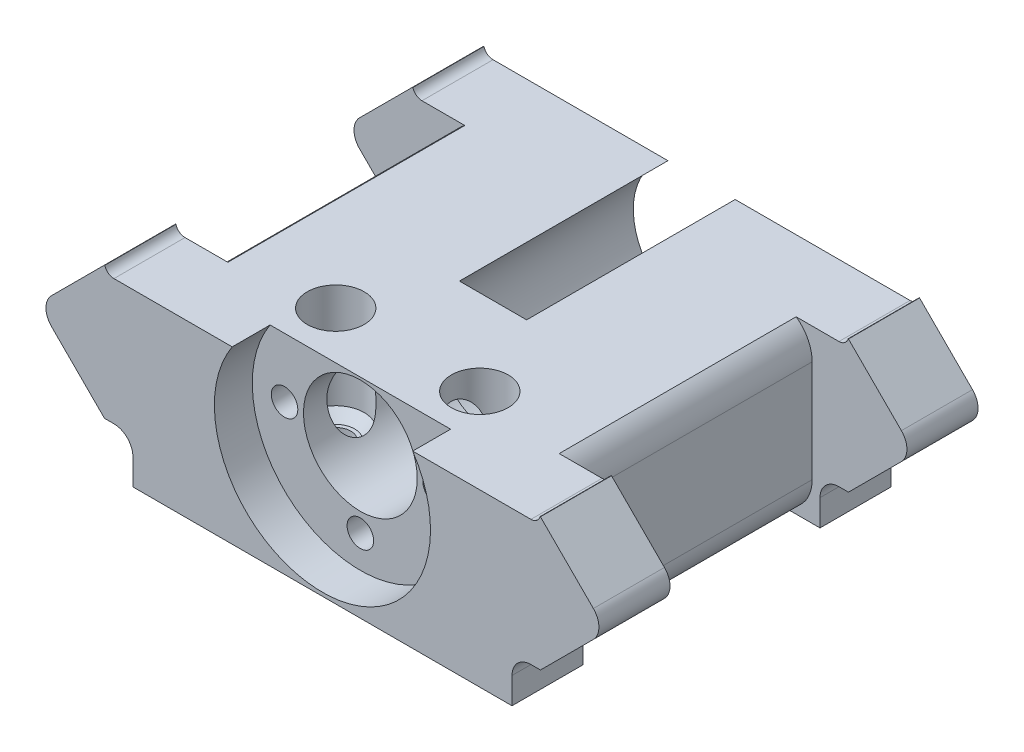
SolidWorks part; units mm, degrees
ref_plane "Front Plane" through (0, 0, 0) normal (0, 0, 1) x (1, 0, 0)
ref_plane "Top Plane" through (0, 0, 0) normal (0, 1, 0) x (1, 0, 0)
ref_plane "Right Plane" through (0, 0, 0) normal (1, 0, 0) x (0, 0, -1)
sketch "Sketch3" plane through (0, 0, 0) normal (0, 0, 1) x (1, 0, 0)
  line L0 (0, 10) -> (0, -10) construction
  line L3 (30, 0) -> (0, 0) construction
  line L5 (-30, 0) -> (30, 0) construction
  line L6 (-28.5858, 1.4142) -> (-23, 7)
  line L7 (-23, 7) -> (23, 7)
  line L8 (0, 10) -> (0, -10) construction
  line L9 (28.5858, 1.4142) -> (23, 7)
  line L10 (28.5858, -1.4142) -> (23, -7)
  line L11 (-28.5858, -1.4142) -> (-23, -7)
  line L12 (-23, -7) -> (-22, -7)
  line L13 (22, -7) -> (23, -7)
  line L14 (-20, -11.77) -> (20, -11.77)
  line L15 (-20, -10) -> (-20, -9)
  line L16 (20, -10) -> (20, -9)
  line L17 (20, -11.77) -> (20, -10)
  line L18 (-20, -11.77) -> (-20, -10)
  arc A0 (-20, -9) -> (-22, -7) centre (-22, -9) ccw
  arc A1 (20, -9) -> (22, -7) centre (22, -9) cw
  arc A2 (28.5858, -1.4142) -> (28.5858, 1.4142) centre (27.1716, 0) ccw
  arc A3 (-28.5858, -1.4142) -> (-28.5858, 1.4142) centre (-27.1716, 0) cw
  circle A4 centre (0, 0) radius 6
  point P17 (0, 7)
  dimension "D3" = 2
  dimension "D4" = 1.77
  dimension "D1" = 45
  dimension "D2" = 46
extrude "Boss-Extrude1" add sketch "Sketch3" along normal blind 40
sketch "Sketch4" plane through (0, -11.77, 0) normal (0, -1, 0) x (1, 0, 0)
  line L0 (-29.1716, 40) -> (-29.1716, 0) construction
  line L1 (-39.1716, 32.5) -> (-19.1716, 32.5)
  line L2 (-39.1716, 32.5) -> (-39.1716, 7.5)
  line L3 (-39.1716, 7.5) -> (-19.1716, 7.5)
  line L4 (-19.1716, 32.5) -> (-19.1716, 7.5)
  line L5 (-39.1716, 32.5) -> (-19.1716, 7.5) construction
  line L6 (-39.1716, 7.5) -> (-19.1716, 32.5) construction
  line L7 (0, 40) -> (0, 0) construction
  line L8 (-20, 40) -> (20, 40) construction
  line L9 (39.1716, 32.5) -> (39.1716, 7.5)
  line L10 (39.1716, 7.5) -> (19.1716, 7.5)
  line L11 (19.1716, 32.5) -> (19.1716, 7.5)
  line L12 (39.1716, 32.5) -> (19.1716, 32.5)
  point P0 (-29.1716, 20)
  dimension "D1" = 20
  dimension "D2" = 25
extrude "Cut-Extrude1" cut sketch "Sketch4" against normal up to next
fillet "Fillet1" radius 4 4 edges at (19.1716, 7, 20) (19.1716, -11.77, 20) (-19.1716, -11.77, 20) (-19.1716, 7, 20)
sketch "Sketch5" plane through (0, 0, 40) normal (0, 0, 1) x (1, 0, 0)
  circle A0 centre (0, 0) radius 11.4
extrude "Cut-Extrude2" cut sketch "Sketch5" against normal blind 4
sketch "Sketch6" plane through (0, 0, 36) normal (0, 0, 1) x (1, 0, 0)
  circle A0 centre (0, 0) radius 8 construction
  circle A1 centre (0, -8) radius 1.4
  circle A2 centre (-8, 0) radius 1.4
  circle A3 centre (8, 0) radius 1.4
extrude "Cut-Extrude3" cut sketch "Sketch6" against normal blind 14
sketch "Sketch7" plane through (0, 0, 0) normal (0, 0, -1) x (-1, 0, 0)
  line L0 (-23, 7) -> (23, 7) construction
  line L1 (-22.9991, 7.7333) -> (22.9991, 7.7333)
  line L2 (-22.9991, 7.7333) -> (-22.9991, 7.2667)
  line L3 (-21.9991, 6.2667) -> (21.9991, 6.2667)
  line L4 (22.9991, 7.7333) -> (22.9991, 7.2667)
  line L5 (-22.9991, 7.7333) -> (22.9991, 6.2667) construction
  line L6 (-22.9991, 6.2667) -> (22.9991, 7.7333) construction
  arc A0 (22.9991, 7.2667) -> (21.9991, 6.2667) centre (21.9991, 7.2667) cw
  arc A1 (-22.9991, 7.2667) -> (-21.9991, 6.2667) centre (-21.9991, 7.2667) ccw
  point P0 (0, 7)
  dimension "D1" = 1
extrude "Cut-Extrude4" cut sketch "Sketch7" against normal up to next
sketch "Sketch8" plane through (0, 0, 0) normal (0, 0, -1) x (-1, 0, 0)
  circle A0 centre (0, 0) radius 7.2
extrude "Cut-Extrude5" cut sketch "Sketch8" against normal blind 22
sketch "Эскиз1" plane through (0, -11.77, 0) normal (0, -1, 0) x (1, 0, 0)
  line L0 (0, 40) -> (0, 0) construction
  line L1 (-20, 40) -> (20, 40) construction
  line L2 (-7.6, 31) -> (0, 31) construction
  circle A0 centre (-7.6, 31) radius 1.6
  circle A1 centre (7.6, 31) radius 1.6
  circle A2 centre (0, 2) radius 1.6
  dimension "D2" = 29
  dimension "D1" = 7.6
  dimension "D3" = 9
extrude "Вырез-Вытянуть4" cut sketch "Эскиз1" against normal blind 6
sketch "Эскиз4" plane through (0, -5.77, 0) normal (0, -1, 0) x (1, 0, 0)
  circle A0 centre (-7.6, 31) radius 3
  circle A1 centre (7.6, 31) radius 3
extrude "Вырез-Вытянуть8" cut sketch "Эскиз4" against normal blind 13
sketch "Эскиз5" plane through (0, -11.77, 0) normal (0, -1, 0) x (1, 0, 0)
  circle A1 centre (0, 2) radius 2.5
extrude "Вырез-Вытянуть9" cut sketch "Эскиз5" against normal blind 10 from offset 3 offset against normal yes
chamfer "Фаска1" distance 1 angle 45 2 edges at (-7.6, -5.77, 28) (7.6, -5.77, 28)
chamfer "Фаска2" distance 0.8 angle 45 1 edges at (0, -8.77, 4.5)
